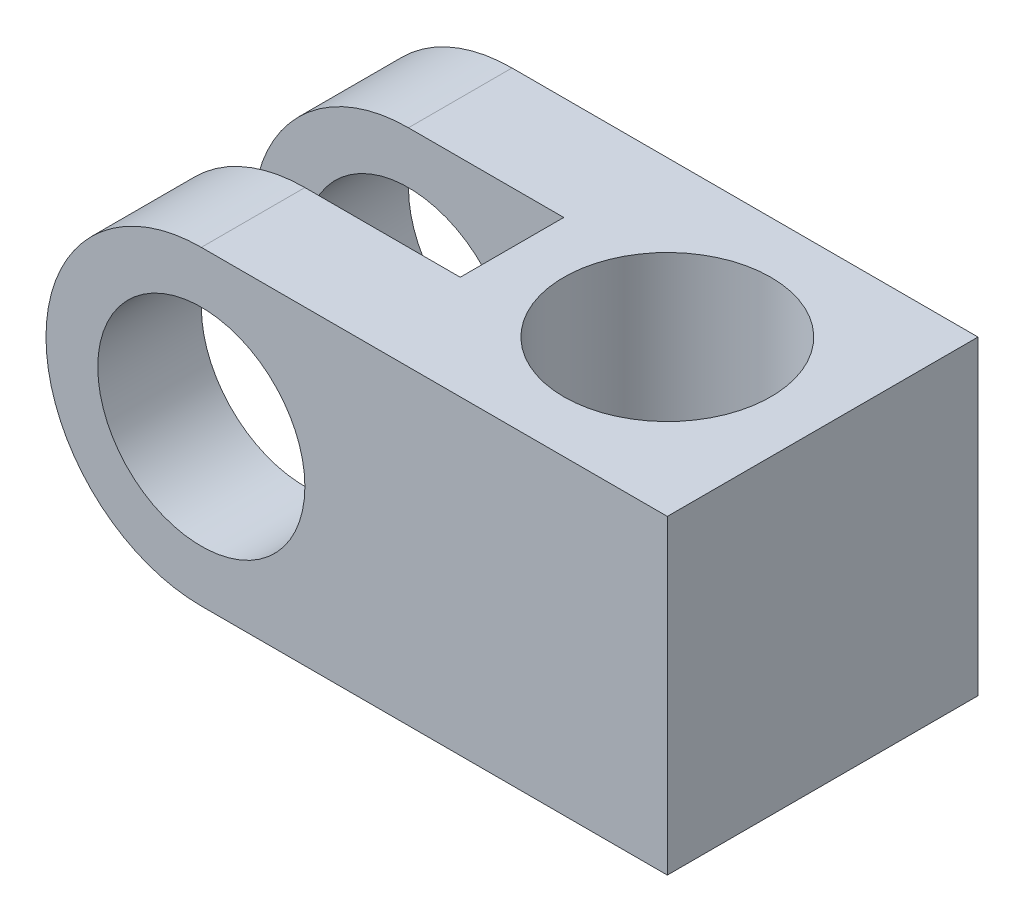
SolidWorks part; units mm, degrees
ref_plane "Front Plane" through (0, 0, 0) normal (0, 0, 1) x (1, 0, 0)
ref_plane "Top Plane" through (0, 0, 0) normal (0, 1, 0) x (1, 0, 0)
ref_plane "Right Plane" through (0, 0, 0) normal (1, 0, 0) x (0, 0, -1)
sketch "Sketch1" plane through (0, 0, 0) normal (0, 1, 0) x (1, 0, 0)
  line L0 (-15, 5) -> (-15, 15) construction
  line L1 (-45, 15) -> (15, 15)
  line L2 (-45, 15) -> (-45, 5)
  line L3 (-45, -15) -> (15, -15)
  line L4 (15, 15) -> (15, -15)
  line L5 (0, 0) -> (15, 0) construction
  line L6 (-45, -5) -> (-45, -15)
  line L7 (-45, 5) -> (-15, 5)
  line L8 (-15, 5) -> (-15, -5)
  line L9 (-15, -5) -> (-45, -5)
  circle A0 centre (0, 0) radius 10
  dimension "D1" = 20
  dimension "D2" = 30
  dimension "D3" = 15
  dimension "D4" = 60
  dimension "D5" = 10
extrude "Boss-Extrude1" add sketch "Sketch1" along normal mid plane 30
sketch "Sketch2" plane through (0, 0, 15) normal (0, 0, 1) x (1, 0, 0)
  line L0 (-30, 0) -> (0, 0) construction
  circle A0 centre (-30, 0) radius 10
  dimension "D2" = 20
  dimension "D1" = 30
extrude "Cut-Extrude1" cut sketch "Sketch2" against normal through all
fillet "Fillet1" radius 15 4 edges at (-45, -15, -10) (-45, 15, -10) (-45, -15, 10) (-45, 15, 10)
